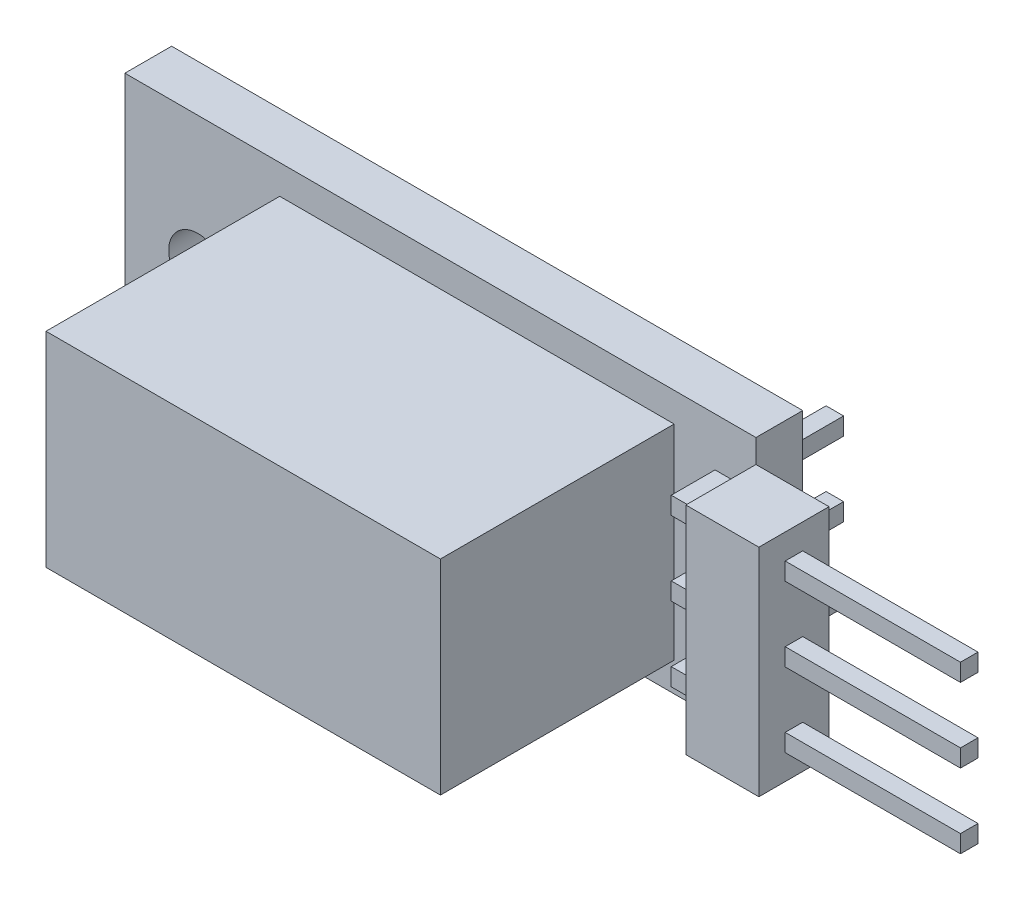
SolidWorks part; units mm, degrees
material "Epoxy, renforcé"
ref_plane "Plan de face" through (0, 0, 0) normal (0, 0, 1) x (1, 0, 0)
ref_plane "Plan de dessus" through (0, 0, 0) normal (0, 1, 0) x (1, 0, 0)
ref_plane "Plan de droite" through (0, 0, 0) normal (1, 0, 0) x (0, 0, -1)
sketch "Esquisse1" plane through (0, 0, 0) normal (0, 0, 1) x (1, 0, 0)
  line L1 (0, 0) -> (21.6, 0)
  line L2 (0, 0) -> (0, 9)
  line L3 (0, 9) -> (21.6, 9)
  line L4 (21.6, 0) -> (21.6, 9)
  dimension "D1" = 9
  dimension "D2" = 21.6
extrude "Boss.-Extru.1" add sketch "Esquisse1" along normal blind 1.6
sketch "Esquisse2" plane through (0, 0, 1.6) normal (0, 0, 1) x (1, 0, 0)
  line L0 (18.8, 4.5) -> (21.6, 4.5) construction
  line L1 (5.3, 1) -> (18.8, 1)
  line L2 (5.3, 1) -> (5.3, 8)
  line L3 (5.3, 8) -> (18.8, 8)
  line L4 (18.8, 1) -> (18.8, 8)
  line L5 (21.6, 0) -> (21.6, 9) construction
  line L6 (0, 9) -> (0, 0) construction
  dimension "D1" = 13.5
  dimension "D2" = 7
  dimension "D3" = 5.3
extrude "Boss.-Extru.2" add sketch "Esquisse2" along normal blind 8 and the other way blind 2.5 separate body
sketch "Esquisse3" plane through (0, 0, 1.6) normal (0, 0, 1) x (1, 0, 0)
  line L0 (2.5, 4.5) -> (0, 4.5) construction
  line L1 (0, 9) -> (0, 0) construction
  circle A0 centre (2.5, 4.5) radius 1
  dimension "D1" = 1.5
  dimension "D2" = 2
extrude "Enlèv. mat.-Extru.1" cut sketch "Esquisse3" against normal through all
sketch "Esquisse4" plane through (21.6, 0, 0) normal (1, 0, 0) x (0, 0, -1)
  line L0 (-1.6, 0) -> (-1.6, 9) construction
  line L1 (-1.6, 8.2) -> (-4, 8.2)
  line L2 (-1.6, 8.2) -> (-1.6, 0.8)
  line L3 (-1.6, 0.8) -> (-4, 0.8)
  line L4 (-4, 8.2) -> (-4, 0.8)
  point P6 (-1.6, 4.5)
  dimension "D1" = 2.4
  dimension "D2" = 7.4
extrude "Boss.-Extru.3" add sketch "Esquisse4" along normal blind 2.5 separate body
sketch "Esquisse5" plane through (0, 0.8, 0) normal (0, -1, 0) x (1, 0, 0)
  line L0 (30.1, 3.1) -> (20.2, 3.1)
  line L1 (20.2, 3.1) -> (20.2, -2.2)
  line L2 (20.2, -2.2) -> (20.8, -2.2)
  line L3 (20.8, -2.2) -> (20.8, 2.5)
  line L4 (20.8, 2.5) -> (30.1, 2.5)
  line L5 (30.1, 2.5) -> (30.1, 3.1)
  line L6 (30.1, 2.8) -> (24.1, 2.8) construction
  line L7 (24.1, 4) -> (24.1, 1.6) construction
  line L8 (0, 1.6) -> (21.6, 1.6) construction
  line L9 (21.6, 1.6) -> (21.6, 0) construction
  dimension "D1" = 0.6
  dimension "D2" = 6
  dimension "D3" = 3.8
  dimension "D4" = 0.8
extrude "Boss.-Extru.5" add sketch "Esquisse5" along normal blind 0.6 from offset 1.46 separate body offset against normal yes
pattern_linear "Répétition linéaire1" count 3 spacing 2.54 along (0, 1, 0) of bodies 105
